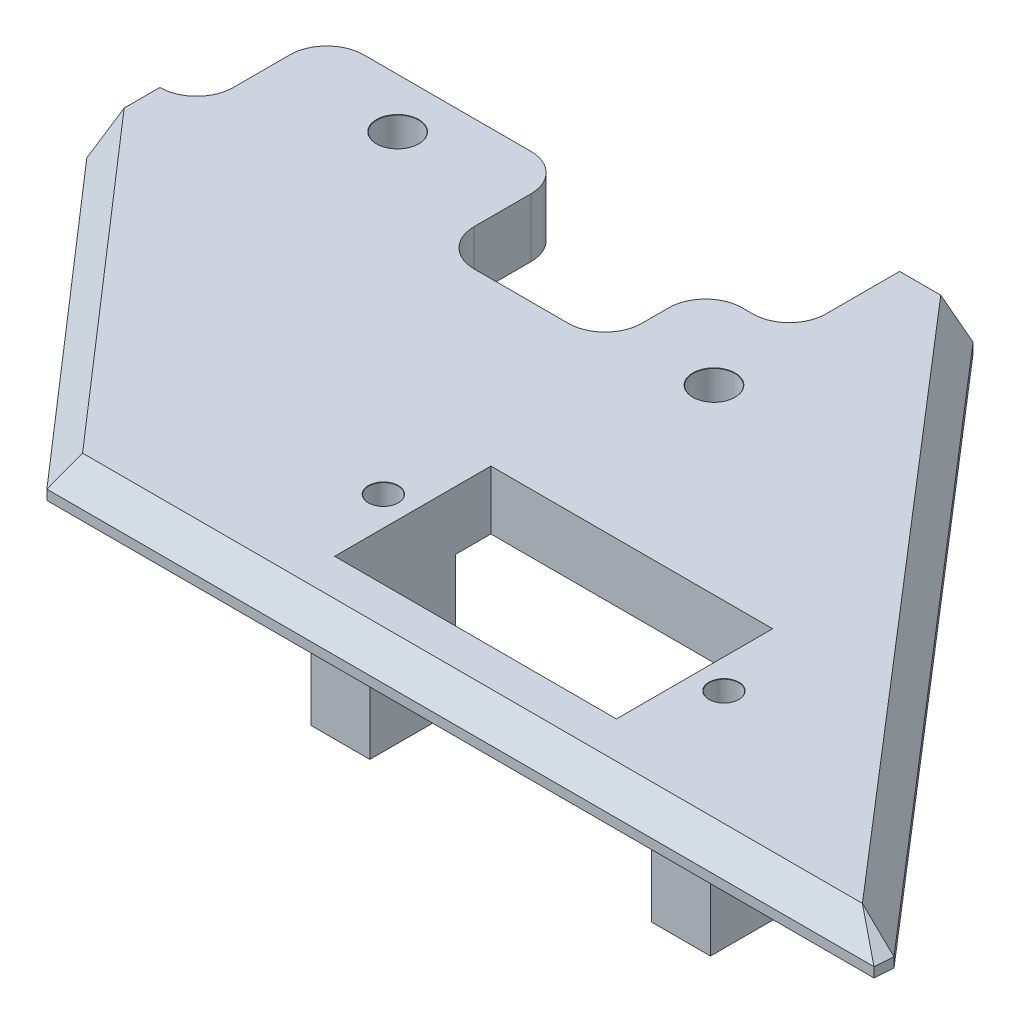
SolidWorks part; units mm, degrees
ref_plane "Front Plane" through (0, 0, 0) normal (0, 0, 1) x (1, 0, 0)
ref_plane "Top Plane" through (0, 0, 0) normal (0, 1, 0) x (1, 0, 0)
ref_plane "Right Plane" through (0, 0, 0) normal (1, 0, 0) x (0, 0, -1)
sketch "Sketch1" plane through (0, 0, 0) normal (0, 1, 0) x (1, 0, 0)
  line L0 (6.83, 0) -> (-6.83, 0)
  line L1 (-9.83, -3) -> (-9.83, -7.63)
  line L2 (9.83, -3) -> (9.83, -7.63)
  line L3 (-12.83, -7.63) -> (-9.83, -7.63) construction
  line L4 (12.83, -7.63) -> (9.83, -7.63) construction
  line L5 (-12.83, -10.63) -> (-12.83, -16.63)
  line L6 (12.83, -10.63) -> (12.83, -16.63)
  line L7 (-12.83, -16.63) -> (12.83, -16.63)
  arc A0 (-6.83, 0) -> (-9.83, -3) centre (-6.83, -3) ccw
  arc A1 (9.83, -3) -> (6.83, 0) centre (6.83, -3) ccw
  arc A2 (-12.83, -10.63) -> (-9.83, -7.63) centre (-12.83, -7.63) ccw
  arc A3 (9.83, -7.63) -> (12.83, -10.63) centre (12.83, -7.63) ccw
  point P4 (0, 0)
  dimension "D4" = 13.66
  dimension "D1" = 3
  dimension "D2" = 6
  dimension "D3" = 13.66
  dimension "D5" = 4.63
extrude "Boss-Extrude1" add sketch "Sketch1" along normal blind 4.8
sketch "Sketch2" plane through (0, 4.8, 0) normal (0, 1, 0) x (1, 0, 0)
  line L0 (-12.83, -16.63) -> (-12.83, -23.63)
  line L1 (-12.83, -23.63) -> (54.3469, -41.63)
  line L2 (54.3469, -41.63) -> (54.3469, -16.63)
  line L3 (54.3469, -16.63) -> (12.83, -16.63)
  line L4 (-12.83, -16.63) -> (12.83, -16.63) construction
  line L5 (-12.83, -16.63) -> (12.83, -16.63)
  dimension "D1" = 25
  dimension "D2" = 7
  dimension "D3" = 75
extrude "Boss-Extrude2" [suppressed] add sketch "Sketch2" against normal up to surface (127 mm away)
sketch "Sketch9" plane through (0, 4.8, 0) normal (0, 1, 0) x (1, 0, 0)
  line L0 (12.83, -16.63) -> (12.83, -10.63) construction
  line L1 (12.83, -16.63) -> (12.83, -10.63)
  line L2 (12.83, -10.63) -> (20.51, -10.63)
  line L3 (23.51, -7.63) -> (23.51, -5.44)
  line L4 (26.51, -2.44) -> (27.36, -2.44)
  line L5 (30.36, 0.56) -> (30.36, 6.56)
  line L6 (12.83, -16.63) -> (36.36, -16.63)
  line L7 (36.36, -16.63) -> (36.36, 6.56)
  line L8 (36.36, 6.56) -> (30.36, 6.56)
  arc A0 (27.36, -2.44) -> (30.36, 0.56) centre (27.36, 0.56) ccw
  arc A1 (23.51, -5.44) -> (26.51, -2.44) centre (26.51, -5.44) cw
  arc A2 (20.51, -10.63) -> (23.51, -7.63) centre (20.51, -7.63) ccw
  dimension "D1" = 3
  dimension "D2" = 7.68
  dimension "D3" = 2.19
  dimension "D4" = 6
  dimension "D5" = 0.85
  dimension "D6" = 6
extrude "Boss-Extrude3" add sketch "Sketch9" against normal up to surface (4.8 mm away) up to face at (0, 0, 7.578)
hole_wizard "M3 Clearance Hole2" positions "Sketch7" profile "Sketch8" hole size "M3" standard "ANSI Metric" end condition through all
sketch "Sketch7" plane through (0, 4.8, 0) normal (0, 1, 0) x (1, 0, 0)
  line L0 (0, -4.05) -> (0, 0) construction
  line L1 (29.4813, -1.5613) -> (30.8213, -1.5613) construction
  line L2 (30.8213, -1.5613) -> (30.8213, -9.0513) construction
  arc A0 (27.36, -2.44) -> (30.36, 0.56) centre (27.36, 0.56) ccw construction
  arc A1 (27.36, -2.44) -> (30.36, 0.56) centre (27.36, 0.56) ccw construction
  point P0 (0, -4.05)
  point P5 (30.8213, -9.0513)
  dimension "D1" = 4.05
  dimension "D2" = 1.34
  dimension "D3" = 7.49
sketch "Sketch8" plane through (0, 4.8, 4.05) normal (1, 0, 0) x (0, 0, 1)
  line L0 (0, 0) -> (0, 4.8)
  line L1 (0, 4.8) -> (1.7, 4.8)
  line L2 (1.7, 4.8) -> (1.7, 0.025)
  line L3 (1.7, 0.025) -> (1.725, 0)
  line L5 (1.725, 0) -> (0, 0)
  line L6 (-1.7, 0.025) -> (-1.725, 0) construction
  line L11 (0, -6.35) -> (0, 107.95) construction
  dimension "Thru Hole Dia." = 3.4
  dimension "Thru Hole Depth" = 4.8
  dimension "Near C'Sink Dia." = 3.45
  dimension "Near C'Sink Angle" = 90
sketch "Sketch10" plane through (0, 4.8, 0) normal (0, 1, 0) x (1, 0, 0)
  line L0 (0, -4.05) -> (38.94, -4.05) construction
  line L1 (38.94, -4.05) -> (77.88, -4.05) construction
  line L2 (-12.83, -16.63) -> (-12.83, -41.63)
  line L3 (-12.83, -41.63) -> (77.88, -41.63)
  line L4 (36.36, 6.56) -> (77.88, 6.56)
  line L5 (-12.83, -16.63) -> (36.36, -16.63) construction
  line L6 (36.36, -16.63) -> (36.36, 6.56) construction
  line L7 (36.36, -16.63) -> (36.36, 6.56)
  line L8 (-12.83, -16.63) -> (36.36, -16.63)
  line L9 (77.88, 6.56) -> (77.88, -41.63)
  dimension "D1" = 38.94
  dimension "D2" = 25
extrude "Boss-Extrude4" add sketch "Sketch10" against normal up to surface (4.8 mm away) up to face at (0, 0, 5.75)
sketch "Sketch11" plane through (0, 4.8, 0) normal (0, 1, 0) x (1, 0, 0)
  line L0 (-12.83, -16.63) -> (77.88, -16.63) construction
  line L1 (-12.83, -10.63) -> (-12.83, -41.63) construction
  line L2 (77.88, -41.63) -> (77.88, 6.56) construction
  line L3 (0, -4.05) -> (38.94, -4.05) construction
  line L4 (50.44, -23.88) -> (27.44, -23.88)
  line L5 (50.44, -23.88) -> (50.44, -36.63)
  line L6 (50.44, -36.63) -> (27.44, -36.63)
  line L7 (27.44, -23.88) -> (27.44, -36.63)
  line L8 (50.44, -23.88) -> (27.44, -36.63) construction
  line L9 (50.44, -36.63) -> (27.44, -23.88) construction
  line L10 (38.94, -4.05) -> (38.94, -30.255) construction
  line L11 (-12.83, -41.63) -> (77.88, -41.63) construction
  circle A0 centre (0, -4.05) radius 1.725 construction
  circle A1 centre (0, -4.05) radius 1.725 construction
  point P6 (38.94, -30.255)
  dimension "D1" = 6
  dimension "D2" = 38.94
  dimension "D3" = 23
  dimension "D4" = 12.75
  dimension "D5" = 5
extrude "Cut-Extrude1" cut sketch "Sketch11" against normal up to surface (4.8 mm away) up to face at (0, 0, 5.75)
hole_wizard "M2 Clearance Hole1" positions "Sketch12" profile "Sketch13" hole size "M2" standard "ANSI Metric" end condition through all
sketch "Sketch12" plane through (0, 4.8, 0) normal (0, 1, 0) x (1, 0, 0)
  line L0 (27.44, -23.88) -> (27.44, -36.63) construction
  line L1 (27.44, -23.88) -> (27.44, -36.63) construction
  line L2 (25.04, -30.255) -> (52.84, -30.255) construction
  line L3 (50.44, -23.88) -> (27.44, -23.88) construction
  line L4 (50.44, -23.88) -> (27.44, -23.88) construction
  point P0 (25.04, -30.255)
  point P2 (52.84, -30.255)
  point P6 (27.44, -30.255)
  point P12 (38.94, -30.255)
  point P13 (38.94, -23.88)
  dimension "D1" = 27.8
sketch "Sketch13" plane through (25.04, 4.8, 30.255) normal (1, 0, 0) x (0, 0, 1)
  line L0 (0, 0) -> (0, 4.8)
  line L1 (0, 4.8) -> (1.2, 4.8)
  line L2 (1.2, 4.8) -> (1.2, 0.025)
  line L3 (1.2, 0.025) -> (1.225, 0)
  line L5 (1.225, 0) -> (0, 0)
  line L6 (-1.2, 0.025) -> (-1.225, 0) construction
  line L11 (0, -6.35) -> (0, 107.95) construction
  dimension "Thru Hole Dia." = 2.4
  dimension "Thru Hole Depth" = 4.8
  dimension "Near C'Sink Dia." = 2.45
  dimension "Near C'Sink Angle" = 90
sketch "Sketch14" plane through (0, 4.8, 0) normal (0, 1, 0) x (1, 0, 0)
  line L0 (-12.83, -16.59) -> (8.9523, -41.63)
  line L1 (-12.83, -10.63) -> (-12.83, -41.63) construction
  line L2 (-12.83, -41.63) -> (77.88, -41.63) construction
  line L3 (8.9523, -41.63) -> (-12.83, -41.63)
  line L4 (-12.83, -41.63) -> (-12.83, -16.59)
  line L5 (36.36, 6.56) -> (77.88, -41.63)
  line L6 (77.88, 6.56) -> (30.36, 6.56) construction
  line L7 (77.88, -41.63) -> (77.88, 6.56) construction
  line L8 (36.36, 6.56) -> (77.88, 6.56)
  line L9 (77.88, 6.56) -> (77.88, -41.63)
  line L10 (-12.83, -16.59) -> (77.88, -16.59) construction
  dimension "D1" = 5.96
  dimension "D2" = 48.98
  dimension "D3" = 6
extrude "Cut-Extrude2" cut sketch "Sketch14" against normal up to surface (4.8 mm away) up to face at (25.04, 0, 31.455)
chamfer "Chamfer2" distance 2 angle 45 7 edges at (77.88, 2.4, 41.63) (57.12, 4.8, 17.535) (43.4161, 0, 41.63) (43.4161, 4.8, 41.63) (-1.9389, 4.8, 29.11) (57.12, 0, 17.535) (-1.9389, 0, 29.11)
sketch "Sketch15" plane through (0, 4.8, 0) normal (0, 1, 0) x (1, 0, 0)
  line L1 (9.8633, -16.6327) -> (9.8633, -39.63)
  line L2 (9.8633, -39.63) -> (-10.142, -16.6327)
  line L3 (9.8633, -16.6327) -> (-10.142, -16.6327)
  line L4 (-12.83, -13.5427) -> (9.8633, -39.63) construction
  dimension "D1" = 3.09
extrude "Boss-Extrude5" [suppressed] add sketch "Sketch15" along normal blind 30
sketch "Sketch16" plane through (0, 0, 0) normal (0, -1, 0) x (1, 0, 0)
  line L5 (50.44, 23.88) -> (50.44, 36.63) construction
  line L6 (27.44, 33.755) -> (22.64, 33.755)
  line L11 (27.44, 33.755) -> (27.44, 26.755)
  line L12 (27.44, 26.755) -> (22.64, 26.755)
  line L14 (22.64, 33.755) -> (22.64, 26.755)
  line L15 (27.44, 33.755) -> (22.64, 26.755) construction
  line L16 (27.44, 26.755) -> (22.64, 33.755) construction
  line L17 (55.24, 33.755) -> (50.44, 33.755)
  line L18 (55.24, 33.755) -> (55.24, 26.755)
  line L19 (55.24, 26.755) -> (50.44, 26.755)
  line L20 (50.44, 33.755) -> (50.44, 26.755)
  line L21 (55.24, 33.755) -> (50.44, 26.755) construction
  line L22 (55.24, 26.755) -> (50.44, 33.755) construction
  point P0 (25.04, 30.255)
  point P6 (52.84, 30.255)
  dimension "D1" = 7
extrude "Boss-Extrude6" add sketch "Sketch16" along normal blind 11
sketch "Sketch17" plane through (0, -11, 0) normal (0, -1, 0) x (1, 0, 0)
  circle A0 centre (25.04, 30.255) radius 1.225 construction
  circle A1 centre (52.84, 30.255) radius 1.225 construction
  circle A2 centre (25.04, 30.255) radius 1.225
  circle A3 centre (52.84, 30.255) radius 1.225
extrude "Cut-Extrude3" cut sketch "Sketch17" against normal blind 11
sketch "Sketch18" plane through (0, -11, 0) normal (0, -1, 0) x (1, 0, 0)
  line L1 (25.04, 27.9456) -> (27.04, 29.1003)
  line L2 (27.04, 29.1003) -> (27.04, 31.4097)
  line L3 (27.04, 31.4097) -> (25.04, 32.5644)
  line L4 (25.04, 32.5644) -> (23.04, 31.4097)
  line L5 (23.04, 31.4097) -> (23.04, 29.1003)
  line L6 (23.04, 29.1003) -> (25.04, 27.9456)
  line L7 (52.84, 27.9456) -> (54.84, 29.1003)
  line L8 (54.84, 29.1003) -> (54.84, 31.4097)
  line L9 (54.84, 31.4097) -> (52.84, 32.5644)
  line L10 (52.84, 32.5644) -> (50.84, 31.4097)
  line L11 (50.84, 31.4097) -> (50.84, 29.1003)
  line L12 (50.84, 29.1003) -> (52.84, 27.9456)
  circle A0 centre (25.04, 30.255) radius 2 construction
  circle A1 centre (52.84, 30.255) radius 2 construction
  dimension "D1" = 4
extrude "Cut-Extrude4" cut sketch "Sketch18" against normal blind 1.75
